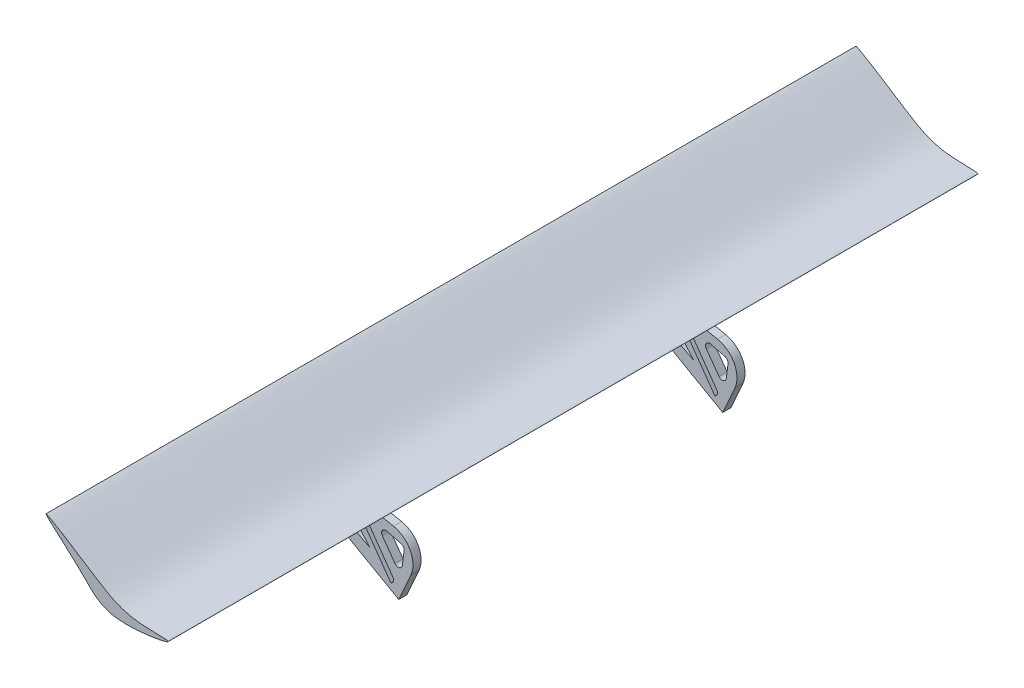
SolidWorks part; units mm, degrees
material "Nylon 101"
ref_plane "Front Plane" through (0, 0, 0) normal (0, 0, 1) x (1, 0, 0)
ref_plane "Top Plane" through (0, 0, 0) normal (0, 1, 0) x (1, 0, 0)
ref_plane "Right Plane" through (0, 0, 0) normal (1, 0, 0) x (0, 0, -1)
sketch "Sketch1" plane through (0, 0, 0) normal (0, 0, 1) x (1, 0, 0)
  spline S0 degree 3 poles (45.4365, 4.6681) (-7.225, -5.268) (-19.9753, 13.1996) (-59.3182, 45.3221) (-9.9104, 13.0298) (5.4953, 3.6482) (45.4365, 4.6681) (-7.225, -5.268) (-19.9753, 13.1996) knots -0.47099 -0.273093 -0.184304 0 0.168703 0.330073 0.52901 0.726907 0.815696 1 1.168703 1.330073 1.52901 only from (0, 0) to (0, 0)
  dimension "D1" = 76.2
extrude "Boss-Extrude1" add sketch "Sketch1" along normal blind 254 and the other way blind 254
sketch "Sketch3" plane through (0, 0, 254) normal (0, 0, 1) x (1, 0, 0)
  line L0 (-49.6974, 58.1399) -> (49.1993, 19.1568)
  line L1 (-59.7816, 14.484) -> (-8.4195, -27.2542)
  line L2 (8.2546, -30.3762) -> (40.0975, -20.0989)
  line L3 (52.4163, -3.1784) -> (52.4163, 14.4307)
  line L4 (-56.225, 55.4257) -> (-64.8948, 35.3239)
  arc A0 (40.0975, -20.0989) -> (52.4163, -3.1784) centre (34.6363, -3.1784) ccw
  arc A1 (-8.4195, -27.2542) -> (8.2546, -30.3762) centre (2.7935, -13.4557) ccw
  arc A2 (-59.7816, 14.484) -> (-64.8948, 35.3239) centre (-48.5686, 28.2825) cw
  arc A3 (49.1993, 19.1568) -> (52.4163, 14.4307) centre (47.3363, 14.4307) cw
  arc A4 (-49.6974, 58.1399) -> (-56.225, 55.4257) centre (-51.5603, 53.4138) ccw
  dimension "D1" = 17.78
  dimension "D2" = 5.08
extrude "Boss-Extrude2" [suppressed] add sketch "Sketch3" along normal blind 7.62
mirror "Mirror1" [suppressed] about plane through (0, 0, 0) normal (0, 0, 1)
sketch "Sketch5" plane through (0, 0, 0) normal (0, 0, 1) x (1, 0, 0)
  line L0 (-27.735, 18.7219) -> (-16.2648, -18.1466)
  line L1 (-9.2408, -26.8701) -> (29.1609, -48.6869)
  line L2 (29.1609, -48.6869) -> (36.7712, -31.6686)
  line L3 (25.8873, -10.5111) -> (14.1913, -8.1397)
  line L4 (8.726, -5.8573) -> (0, 0)
  line L5 (-14.3369, 0) -> (-8.0343, -19.689)
  line L6 (-8.0343, -19.689) -> (11.0592, -29.5227)
  line L7 (-14.3369, 0) -> (11.0592, -29.5227)
  line L10 (24.2508, -42.1672) -> (1.4669, -9.9587)
  line L11 (-27.735, 18.7219) -> (0, 0)
  line L12 (2.0736, -6.4183) -> (2.6348, -6.0213)
  line L13 (2.6348, -6.0213) -> (25.4392, -38.2587)
  line L14 (24.7106, -41.8802) -> (24.2508, -42.1672)
  line L15 (21.5698, -15.3186) -> (30.6251, -17.5963)
  line L16 (32.5247, -20.384) -> (31.4023, -29.099)
  line L17 (26.8234, -30.2609) -> (18.8905, -19.2682)
  arc A0 (36.7712, -31.6686) -> (25.8873, -10.5111) centre (22.8589, -25.4472) ccw
  arc A1 (-16.2648, -18.1466) -> (-9.2408, -26.8701) centre (-1.7128, -13.6193) ccw
  arc A2 (14.1913, -8.1397) -> (8.726, -5.8573) centre (17.2197, 6.7964) cw
  arc A3 (2.0736, -6.4183) -> (1.4669, -9.9587) centre (3.5405, -8.4919) ccw
  arc A4 (25.4392, -38.2587) -> (24.7106, -41.8802) centre (23.3655, -39.7255) cw
  arc A5 (31.4023, -29.099) -> (26.8234, -30.2609) centre (28.8831, -28.7745) cw
  arc A6 (21.5698, -15.3186) -> (18.8905, -19.2682) centre (20.9502, -17.7818) ccw
  arc A7 (30.6251, -17.5963) -> (32.5247, -20.384) centre (30.0055, -20.0595) cw
  spline S0 degree 3 poles (-19.9753, 13.1996) (-7.225, -5.268) (45.4365, 4.6681) (5.4953, 3.6482) (-9.9104, 13.0298) (-59.3182, 45.3221) (-19.9753, 13.1996) (-7.225, -5.268) (45.4365, 4.6681) knots -0.52901 -0.330073 -0.168703 0 0.184304 0.273093 0.47099 0.669927 0.831297 1 1.184304 1.273093 1.47099 only from (0, 0) to (0, 0) construction
  dimension "D1" = 15.24
  dimension "D2" = 15.24
  dimension "D3" = 2.54
extrude "Boss-Extrude3" add sketch "Sketch5" along normal blind 5.08 from offset 101.6
extrude "Boss-Extrude4" add sketch "Sketch5<3>" along normal blind 5.08 from offset 101.6 offset against normal yes
sketch "Sketch5<3>" plane through (0, 0, 0) normal (0, 0, 1) x (1, 0, 0) same geometry as "Sketch5"
